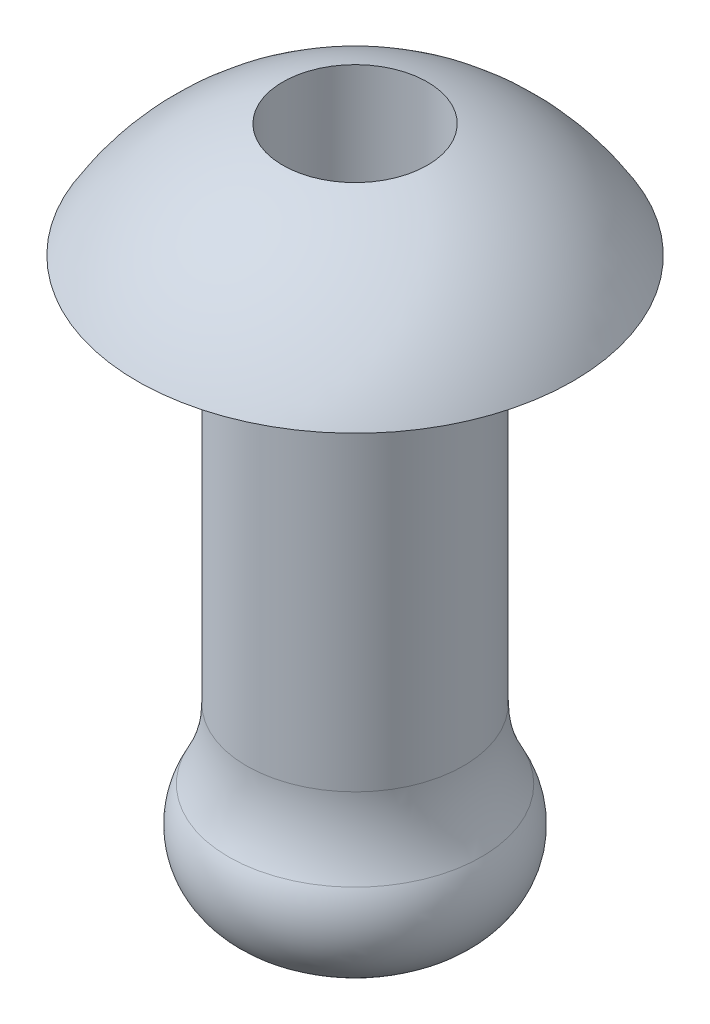
SolidWorks part; units mm, degrees
ref_plane "前视" through (0, 0, 0) normal (0, 0, 1) x (1, 0, 0)
ref_plane "上视" through (0, 0, 0) normal (0, 1, 0) x (1, 0, 0)
ref_plane "右视" through (0, 0, 0) normal (1, 0, 0) x (0, 0, -1)
sketch "草图1" plane through (0, 0, 0) normal (0, 0, 1) x (1, 0, 0)
  line L0 (-61.5701, 42.6476) -> (-55.5381, 42.6476)
  line L1 (-60.0541, 42.6476) -> (-60.0541, 37.2782)
  line L2 (-58.5541, 44.3717) -> (-58.5541, 33.247)
  line L3 (-57.0541, 37.2782) -> (-57.0541, 42.6476)
  arc A0 (-55.5381, 42.6476) -> (-61.5701, 42.6476) centre (-58.5541, 40.8717) ccw
  arc A1 (-56.7906, 36.2859) -> (-57.0541, 37.2782) centre (-55.0541, 37.2782) cw
  arc A2 (-60.3176, 36.2859) -> (-56.7906, 36.2859) centre (-58.5541, 35.2782) ccw
  arc A3 (-60.3176, 36.2859) -> (-60.0541, 37.2782) centre (-62.0541, 37.2782) ccw
  point P6 (-57.0541, 36.6476)
  point P13 (-60.0541, 36.6476)
  dimension "D3" = 7
  dimension "D5" = 2
  dimension "D6" = 2
  dimension "D1" = 3
  dimension "D2" = 6
  dimension "D4" = 1.5
revolve "旋转1" add sketch "草图1" angle 360 about L2 region at (-57.3738, 43.3543, 0) region at (-57.7453, 37.8578, 0)
sketch "草图2" plane through (0, 0, 0) normal (0, 1, 0) x (1, 0, 0)
  circle A0 centre (-58.5541, 0) radius 1
extrude "切除-拉伸1" cut sketch "草图2" along normal blind 50
sketch "草图3" plane through (0, 0, 0) normal (0, 0, 1) x (1, 0, 0)
  line L1 (-60.8476, 34.8373) -> (-30.8476, 34.8373)
  line L2 (-60.8476, 34.8373) -> (-60.8476, 33.2943)
  line L3 (-60.8476, 33.2943) -> (-30.8476, 33.2943)
  line L4 (-30.8476, 34.8373) -> (-30.8476, 33.2943)
  dimension "D1" = 30
extrude "切除-拉伸2" cut sketch "草图3" against normal mid plane 10
fillet "圆角1" radius 1 1 edges at (-58.5541, 34.8373, 1.9827)
